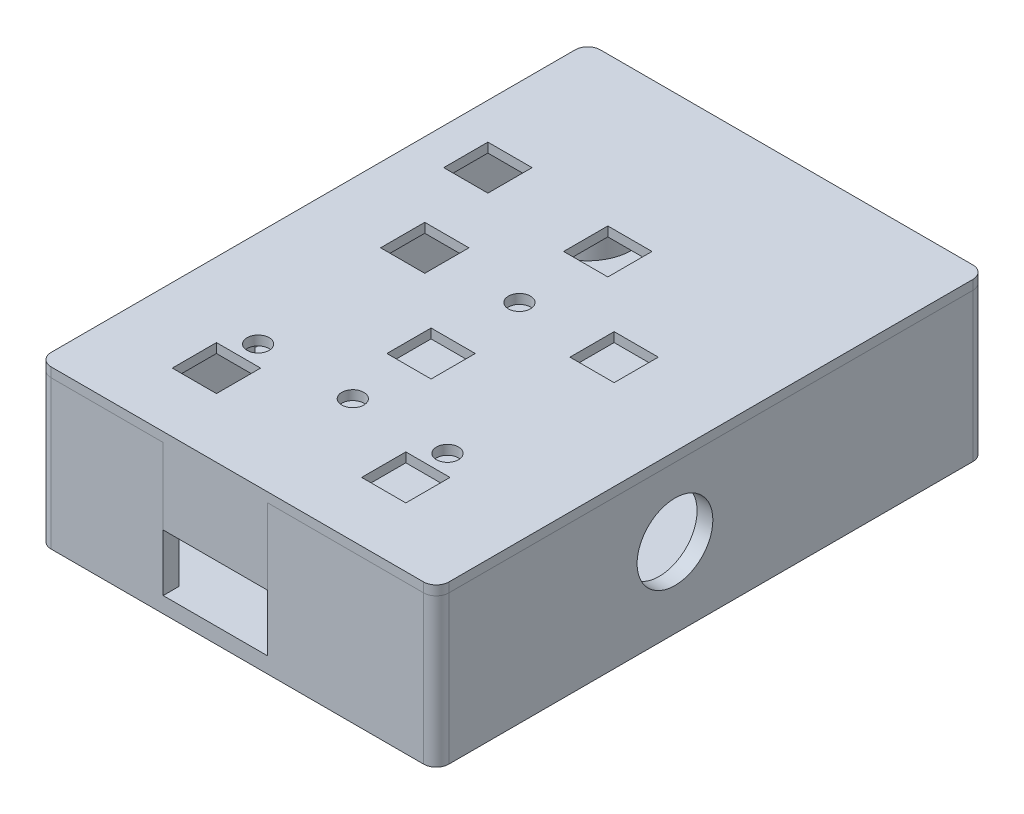
SolidWorks part; units mm, degrees
ref_plane "前视基准面" through (0, 0, 0) normal (0, 0, 1) x (1, 0, 0)
ref_plane "上视基准面" through (0, 0, 0) normal (0, 1, 0) x (1, 0, 0)
ref_plane "右视基准面" through (0, 0, 0) normal (1, 0, 0) x (0, 0, -1)
sketch "草图1" plane through (0, 0, 0) normal (0, 1, 0) x (1, 0, 0)
  line L0 (-11.76, -41) -> (-11.76, -43.5)
  line L1 (-26, 38) -> (26, 38) construction
  line L2 (-26, 38) -> (-26, -38) construction
  line L3 (-26, -38) -> (26, -38) construction
  line L4 (26, 38) -> (26, -38) construction
  line L5 (-26, 38) -> (26, -38) construction
  line L6 (-26, -38) -> (26, 38) construction
  line L7 (-29, 41) -> (29, 41)
  line L8 (-29, 41) -> (-29, -41)
  line L9 (-29, -41) -> (29, -41)
  line L10 (29, 41) -> (29, -41)
  line L11 (-29, 41) -> (29, -41) construction
  line L12 (-29, -41) -> (29, 41) construction
  line L13 (-29.5, 43.5) -> (29.5, 43.5)
  line L14 (-31.5, 41.5) -> (-31.5, -41.5)
  line L15 (-29.5, -43.5) -> (29.5, -43.5)
  line L16 (31.5, 41.5) -> (31.5, -41.5)
  line L17 (-31.5, 43.5) -> (31.5, -43.5) construction
  line L18 (-31.5, -43.5) -> (31.5, 43.5) construction
  line L19 (4.74, -41) -> (4.74, -43.5)
  line L20 (23.65, 43.5) -> (23.65, 41)
  line L21 (-23.35, 43.5) -> (-23.35, 41)
  line L22 (-16.35, 43.5) -> (-16.35, 41)
  line L23 (-31.5, 0.32) -> (-29, 0.32)
  line L24 (-31.5, -11.68) -> (-29, -11.68)
  circle A0 centre (-26, 38) radius 0.75
  circle A1 centre (26, 38) radius 0.75
  circle A2 centre (26, -38) radius 0.75
  circle A3 centre (-26, -38) radius 0.75
  arc A4 (-29.5, -43.5) -> (-31.5, -41.5) centre (-29.5, -41.5) cw
  arc A5 (31.5, -41.5) -> (29.5, -43.5) centre (29.5, -41.5) cw
  arc A6 (29.5, 43.5) -> (31.5, 41.5) centre (29.5, 41.5) cw
  arc A7 (-29.5, 43.5) -> (-31.5, 41.5) centre (-29.5, 41.5) ccw
  arc A8 (-29, -34) -> (-22, -41) centre (-29, -41) cw
  arc A9 (22, -41) -> (29, -34) centre (29, -41) cw
  arc A10 (29, 34) -> (22, 41) centre (29, 41) cw
  arc A11 (-22, 41) -> (-29, 34) centre (-29, 41) cw
  point P0 (0, 0)
  point P10 (0, 0)
  point P15 (0, 0)
  dimension "D3" = 1.5
  dimension "D8" = 2
  dimension "D11" = 7
  dimension "D1" = 76
  dimension "D2" = 52
  dimension "D4" = 3
  dimension "D5" = 3
  dimension "D6" = 2.5
  dimension "D7" = 2.5
  dimension "D9" = 14.24
  dimension "D10" = 16.5
  dimension "D12" = 2.35
  dimension "D13" = 7
  dimension "D14" = 40
  dimension "D15" = 12
  dimension "D16" = 26.32
extrude "凸台-拉伸1" add sketch "草图1" against normal blind 2.5 contours L14 A4 L15 A5 L16 A6 L13 A7
extrude "凸台-拉伸2" add sketch "草图1<4>" along normal blind 3 contours A11 L7 L8 A0 | A10 L10 L7 A1 | A9 L9 L10 A2 | A8 L8 L9 A3 region at (-25.5, 0, 40.901) region at (24.1203, 0, 36.1203) region at (24.1203, 0, -36.1203) region at (-28.901, 0, -37.5)
sketch "草图1<4>" plane through (0, 0, 0) normal (0, 1, 0) x (1, 0, 0) same geometry as "草图1"
extrude "凸台-拉伸4" add sketch "草图1<5>" along normal blind 4.6 separate body contours L13 L21 L7 L20 region at (3.65, 0, -42.25)
sketch "草图1<5>" plane through (0, 0, 0) normal (0, 1, 0) x (1, 0, 0) same geometry as "草图1"
extrude "凸台-拉伸5" add sketch "草图1<6>" along normal blind 21 contours L13 A7 L14 A4 L15 L0 L9 L8 L7 L21 | A6 L13 L20 L7 L10 L9 L19 L15 A5 L16 | L13 A7 L14 L23 L8 L7 L21 region at (-12.1345, 0, 42.25) region at (13.37, 0, 41.9102) region at (-29.7695, 0, -24.1304)
sketch "草图1<6>" plane through (0, 0, 0) normal (0, 1, 0) x (1, 0, 0) same geometry as "草图1"
extrude "凸台-拉伸6" add sketch "草图1<7>" along normal blind 9.4 contours L22 L13 L21 L7 region at (-19.85, 0, -42.25)
sketch "草图1<7>" plane through (0, 0, 0) normal (0, 1, 0) x (1, 0, 0) same geometry as "草图1"
sketch "草图2" plane through (0, 0, -43.5) normal (0, 0, -1) x (-1, 0, 0)
  line L0 (23.35, 9.4) -> (16.35, 9.4) construction
  circle A0 centre (19.85, 9.4) radius 3.5
extrude "切除-拉伸1" cut sketch "草图2" against normal up to next
sketch "草图3" plane through (31.5, 0, 0) normal (1, 0, 0) x (0, 0, -1)
  line L2 (-38, 3) -> (-38, 0) construction
  line L3 (34, 0) -> (-34, 0) construction
  circle A0 centre (-5.68, 10.1) radius 6
  dimension "D2" = 12
  dimension "D1" = 32.32
  dimension "D3" = 10.1
extrude "切除-拉伸2" cut sketch "草图3" against normal up to next
extrude "凸台-拉伸11" add sketch "草图1<8>" along normal blind 7 contours L14 L24 L8 L23 region at (-30.25, 0, 5.68)
sketch "草图1<8>" plane through (0, 0, 0) normal (0, 1, 0) x (1, 0, 0) same geometry as "草图1"
sketch "草图4" plane through (0, 21, 0) normal (0, 1, 0) x (1, 0, 0)
  line L0 (-11.76, -41) -> (-11.76, -43.5)
  line L1 (-26, 38) -> (26, 38) construction
  line L2 (-26, 38) -> (-26, -38) construction
  line L3 (-26, -38) -> (26, -38) construction
  line L4 (26, 38) -> (26, -38) construction
  line L5 (-26, 38) -> (26, -38) construction
  line L6 (-26, -38) -> (26, 38) construction
  line L7 (-29, 41) -> (29, 41)
  line L8 (-29, 41) -> (-29, -41)
  line L9 (-29, -41) -> (29, -41)
  line L10 (29, 41) -> (29, -41)
  line L11 (-29, 41) -> (29, -41) construction
  line L12 (-29, -41) -> (29, 41) construction
  line L13 (-29.5, 43.5) -> (29.5, 43.5)
  line L14 (-31.5, 41.5) -> (-31.5, -41.5)
  line L15 (-29.5, -43.5) -> (29.5, -43.5)
  line L16 (31.5, 41.5) -> (31.5, -41.5)
  line L17 (-31.5, 43.5) -> (31.5, -43.5) construction
  line L18 (-31.5, -43.5) -> (31.5, 43.5) construction
  line L19 (4.74, -41) -> (4.74, -43.5)
  line L20 (23.65, 43.5) -> (23.65, 41)
  line L21 (-23.35, 43.5) -> (-23.35, 41)
  line L22 (-16.35, 43.5) -> (-16.35, 41)
  line L23 (-31.5, 0.32) -> (-29, 0.32)
  line L24 (-31.5, -11.68) -> (-29, -11.68)
  line L25 (10.25, 5.93) -> (17.25, 5.93)
  line L26 (-16.35, 43.5) -> (-23.35, 43.5) construction
  line L27 (-11.76, -41) -> (-11.76, -43.5) construction
  line L28 (4.74, -41) -> (4.74, -43.5) construction
  line L29 (-29, -41) -> (-11.76, -41) construction
  line L30 (29, 41) -> (29, -41) construction
  line L31 (31.5, 41.5) -> (31.5, -41.5) construction
  line L32 (-23.35, 43.5) -> (-23.35, 41) construction
  line L33 (-16.35, 43.5) -> (-16.35, 41) construction
  line L34 (23.65, 43.5) -> (23.65, 41) construction
  line L35 (-4.75, 19.93) -> (2.25, 19.93)
  line L36 (-4.75, 19.93) -> (-4.75, 12.93)
  line L37 (-4.75, 12.93) -> (2.25, 12.93)
  line L38 (2.25, 19.93) -> (2.25, 12.93)
  line L39 (-4.75, 19.93) -> (2.25, 12.93) construction
  line L40 (-4.75, 12.93) -> (2.25, 19.93) construction
  line L41 (10.25, 5.93) -> (10.25, -1.07)
  line L42 (10.25, -1.07) -> (17.25, -1.07)
  line L43 (17.25, 5.93) -> (17.25, -1.07)
  line L44 (10.25, 5.93) -> (17.25, -1.07) construction
  line L45 (10.25, -1.07) -> (17.25, 5.93) construction
  line L46 (-19.75, 5.93) -> (-12.75, 5.93)
  line L47 (-19.75, 5.93) -> (-19.75, -1.07)
  line L48 (-19.75, -1.07) -> (-12.75, -1.07)
  line L49 (-12.75, 5.93) -> (-12.75, -1.07)
  line L50 (-19.75, 5.93) -> (-12.75, -1.07) construction
  line L51 (-19.75, -1.07) -> (-12.75, 5.93) construction
  line L52 (-4.75, -8.07) -> (2.25, -8.07)
  line L53 (-4.75, -8.07) -> (-4.75, -15.07)
  line L54 (-4.75, -15.07) -> (2.25, -15.07)
  line L55 (2.25, -8.07) -> (2.25, -15.07)
  line L56 (-4.75, -8.07) -> (2.25, -15.07) construction
  line L57 (-4.75, -15.07) -> (2.25, -8.07) construction
  line L58 (-19.75, -27.07) -> (-12.75, -27.07)
  line L59 (-19.75, -27.07) -> (-19.75, -34.07)
  line L60 (-19.75, -34.07) -> (-12.75, -34.07)
  line L61 (-12.75, -27.07) -> (-12.75, -34.07)
  line L62 (-19.75, -27.07) -> (-12.75, -34.07) construction
  line L63 (-19.75, -34.07) -> (-12.75, -27.07) construction
  line L64 (10.25, -27.07) -> (17.25, -27.07)
  line L65 (10.25, -27.07) -> (10.25, -34.07)
  line L66 (10.25, -34.07) -> (17.25, -34.07)
  line L67 (17.25, -27.07) -> (17.25, -34.07)
  line L68 (10.25, -27.07) -> (17.25, -34.07) construction
  line L69 (10.25, -34.07) -> (17.25, -27.07) construction
  line L70 (-16.25, 2.43) -> (13.75, 2.43) construction
  line L71 (-1.25, 2.43) -> (-1.25, 16.43) construction
  line L72 (-16.25, -30.57) -> (13.75, -30.57) construction
  line L73 (-1.25, -30.57) -> (-1.25, -11.57) construction
  line L74 (-1.25, 2.43) -> (-1.25, -11.57) construction
  line L75 (-16.25, -23.97) -> (-16.25, -30.57) construction
  line L76 (13.75, -23.97) -> (13.75, -30.57) construction
  line L77 (-16.25, -23.97) -> (13.75, -23.97) construction
  line L78 (-25.75, 21.93) -> (-18.75, 21.93)
  line L79 (-25.75, 21.93) -> (-25.75, 14.93)
  line L80 (-25.75, 14.93) -> (-18.75, 14.93)
  line L81 (-18.75, 21.93) -> (-18.75, 14.93)
  line L82 (-25.75, 21.93) -> (-18.75, 14.93) construction
  line L83 (-25.75, 14.93) -> (-18.75, 21.93) construction
  circle A0 centre (-26, 38) radius 0.75
  circle A1 centre (26, 38) radius 0.75
  circle A2 centre (26, -38) radius 0.75
  circle A3 centre (-26, -38) radius 0.75
  arc A4 (-29.5, -43.5) -> (-31.5, -41.5) centre (-29.5, -41.5) cw
  arc A5 (31.5, -41.5) -> (29.5, -43.5) centre (29.5, -41.5) cw
  arc A6 (29.5, 43.5) -> (31.5, 41.5) centre (29.5, 41.5) cw
  arc A7 (-29.5, 43.5) -> (-31.5, 41.5) centre (-29.5, 41.5) ccw
  arc A8 (-29, -34) -> (-22, -41) centre (-29, -41) cw
  arc A9 (22, -41) -> (29, -34) centre (29, -41) cw
  arc A10 (29, 34) -> (22, 41) centre (29, 41) cw
  arc A11 (-22, 41) -> (-29, 34) centre (-29, 41) cw
  circle A12 centre (-26, 38) radius 0.75 construction
  arc A13 (-29, 34) -> (-22, 41) centre (-29, 41) ccw construction
  arc A14 (-29.5, 43.5) -> (-31.5, 41.5) centre (-29.5, 41.5) ccw construction
  circle A15 centre (-1.25, 2.43) radius 1.75
  circle A16 centre (-16.25, -23.97) radius 1.75
  circle A17 centre (-1.25, -23.97) radius 1.75
  circle A18 centre (13.75, -23.97) radius 1.75
  point P0 (0, 0)
  point P9 (0, 0)
  point P14 (0, 0)
  point P85 (-1.25, 16.43)
  point P90 (13.75, 2.43)
  point P95 (-16.25, 2.43)
  point P100 (-1.25, -11.57)
  point P105 (-16.25, -30.57)
  point P110 (13.75, -30.57)
  point P130 (-22.25, 18.43)
  line M14 (-31.5, -11.68) -> (-31.5, -41.5)
  arc M15 (-31.5, -41.5) -> (-29.5, -43.5) centre (-29.5, -41.5) ccw
  line M16 (-29.5, -43.5) -> (-11.76, -43.5)
  line M17 (-11.76, -43.5) -> (-11.76, -41)
  line M18 (-11.76, -41) -> (-29, -41)
  line M19 (-29, -41) -> (-29, -11.68)
  line M58 (-29, -11.68) -> (-31.5, -11.68)
  dimension "D4" = 3.5
  dimension "D1" = 7
  dimension "D2" = 30
  dimension "D3" = 14
  dimension "D5" = 19
  dimension "D6" = 7.43
  dimension "D7" = 6.6
  dimension "D8" = 16
  dimension "D9" = 6
  dimension "D10" = 24.75
extrude "凸台-拉伸7" add sketch "草图4" along normal blind 1.5 separate body contours L7 A11 L8 A8 L9 A9 L10 A10 A18 A17 A16 A15 L35 L38 L37 L36 L25 L43 L42 L41 L46 L49 L48 L47 L52 L55 L54 L53 L58 L61 L60 L59 L64 L67 L66 L65 M18 | L23 L14 L8 M58 | L13 A7 L14 L23 L8 L7 L21 | L9 L8 M14 M15 M16 M17 M18 M19 M58 | A8 L9 A3 M19 | L19 L9 L15 M17 | A6 L13 L20 L7 L10 L9 L19 L15 A5 L16 | A9 L9 L10 A2 | A10 L10 L7 A1 | L13 L22 L7 L20 | A11 L7 L8 A0 | L22 L13 L21 L7 | A0 | A1 | A2 | A3 region at (-3.51, 21, 42.25) region at (-12.1345, 21, 42.25) region at (0.3568, 21, -0.5414) region at (-25.5, 21, 40.901) region at (13.37, 21, 41.9102) region at (24.1203, 21, 36.1203) region at (-30.25, 21, 5.68) region at (-29.7695, 21, -24.1304) region at (24.1203, 21, -36.1203) region at (-28.901, 21, -37.5) region at (3.65, 21, -42.25) region at (-19.85, 21, -42.25) region at (-26, 21, -38) region at (26, 21, -38) region at (26, 21, 38) region at (-26, 21, 38)
extrude "凸台-拉伸8" add sketch "草图4<4>" against normal blind 12 contours L19 L9 L15 M17 region at (-3.51, 21, 42.25)
sketch "草图4<4>" plane through (0, 21, 0) normal (0, 1, 0) x (1, 0, 0) same geometry as "草图4"
extrude "凸台-拉伸9" add sketch "草图4<5>" against normal blind 11.5 contours L22 L13 L7 region at (-19.85, 21, -42.25)
sketch "草图4<5>" plane through (0, 21, 0) normal (0, 1, 0) x (1, 0, 0) same geometry as "草图4"
sketch "草图5" plane through (0, 0, -43.5) normal (0, 0, -1) x (-1, 0, 0)
  line L0 (23.35, 9.5) -> (16.35, 9.5) construction
  circle A0 centre (19.85, 9.5) radius 3.5
  dimension "D1" = 7
extrude "切除-拉伸3" cut sketch "草图5" against normal up to next (2.5 mm away)
extrude "凸台-拉伸10" add sketch "草图4<6>" against normal blind 4.4 contours L13 L22 L7 L20 region at (3.65, 21, -42.25)
sketch "草图4<6>" plane through (0, 21, 0) normal (0, 1, 0) x (1, 0, 0) same geometry as "草图4"
extrude "凸台-拉伸12" add sketch "草图4<7>" against normal blind 8.6 contours L23 L14 L8 M58 region at (-30.25, 21, 5.68)
sketch "草图4<7>" plane through (0, 21, 0) normal (0, 1, 0) x (1, 0, 0) same geometry as "草图4"
extrude "凸台-拉伸13" add sketch "草图4<8>" against normal blind 4 contours A11 L7 L8 A0 | A10 L10 L7 A1 | A9 L9 L10 A2 | A8 L9 A3 M19 | A3 | A2 | A1 | A0 region at (-25.5, 21, 40.901) region at (24.1203, 21, 36.1203) region at (24.1203, 21, -36.1203) region at (-28.901, 21, -37.5) region at (-26, 21, -38) region at (26, 21, -38) region at (26, 21, 38) region at (-26, 21, 38)
sketch "草图4<8>" plane through (0, 21, 0) normal (0, 1, 0) x (1, 0, 0) same geometry as "草图4"
